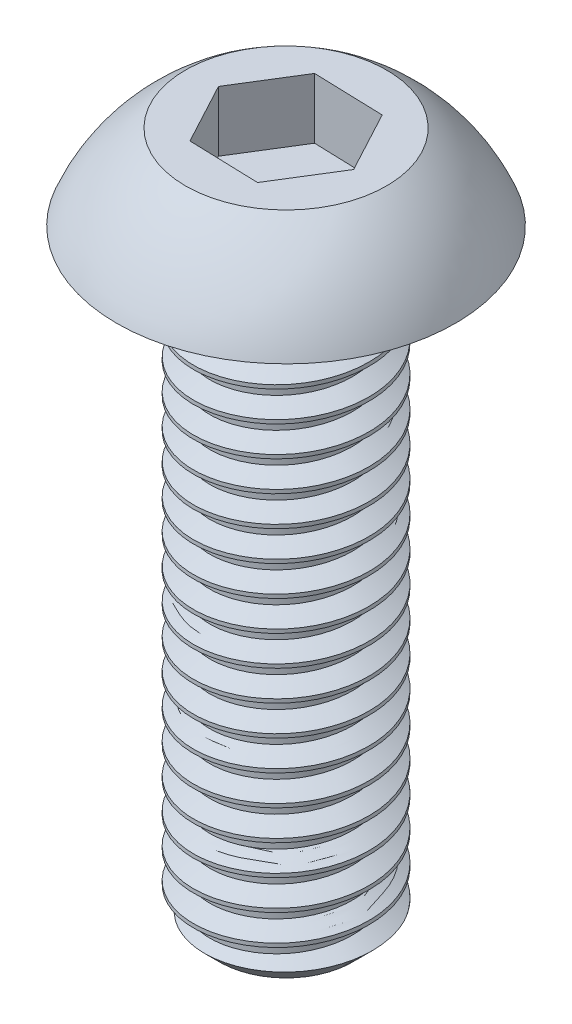
SolidWorks part; units mm, degrees
material "AISI 304"
ref_plane "Front Plane" through (0, 0, 0) normal (0, 0, 1) x (1, 0, 0)
ref_plane "Top Plane" through (0, 0, 0) normal (0, 1, 0) x (1, 0, 0)
ref_plane "Right Plane" through (0, 0, 0) normal (1, 0, 0) x (0, 0, -1)
sketch "Sketch1" plane through (0, 0, 0) normal (1, 0, 0) x (0, 0, -1)
  line L0 (0, 3.928) -> (0, 3.1683) construction
  line L1 (-2.8, 1.2683) -> (-1.45, 1.2683)
  line L2 (-1.45, 1.2683) -> (-1.45, -8.7317)
  line L3 (-1.6623, 2.6683) -> (0, 2.6683)
  line L4 (0, 2.6683) -> (0, -8.7317)
  line L5 (0, -8.7317) -> (-1.45, -8.7317)
  line L6 (0, 2.6683) -> (0, -3.4668) construction
  arc A0 (-2.8, 1.2683) -> (-1.6623, 2.6683) centre (0, 0.1552) cw
  point P10 (0, 3.1683)
  dimension "D1" = 2.9
  dimension "D2" = 5.6
  dimension "D3" = 1.9
  dimension "D4" = 10
  dimension "D5" = 1.4
revolve "Revolve1" add sketch "Sketch1" angle 360 about L0
sketch "Sketch2" plane through (0, 2.6683, 0) normal (0, 1, 0) x (1, 0, 0)
  line L1 (-0.5457, 1.0176) -> (-1.1541, 0.0363)
  line L2 (-1.1541, 0.0363) -> (-0.6085, -0.9814)
  line L3 (-0.6085, -0.9814) -> (0.5457, -1.0176)
  line L4 (0.5457, -1.0176) -> (1.1541, -0.0363)
  line L5 (1.1541, -0.0363) -> (0.6085, 0.9814)
  line L6 (0.6085, 0.9814) -> (-0.5457, 1.0176)
  circle A0 centre (0, 0) radius 1 construction
  dimension "D1" = 2
extrude "Cut-Extrude1" cut sketch "Sketch2" against normal blind 1
chamfer "Chamfer1" distance 0.35 angle 45 1 edges at (0, -8.7317, 1.45)
thread "Thread1" pitch 0.5 method cut profile "Thread Profile1" start angle 0, offset 0, length 20, pitch 0.5, diameter 2.9
ref_plane "Plane1" through (-1.45, 1.2683, 0) normal (0, 0, 1) x (-1, 0, 0)
sketch "Thread Profile1" plane through (-1.45, 1.2683, 0) normal (0, 0, 1) x (-1, 0, 0)
  line L0 (0, 0) -> (0, 0.5) construction
  line L11 (0, 0) -> (0, 0.4375)
  line L12 (0, 0.4375) -> (-0.2706, 0.2812)
  line L13 (-0.2706, 0.2812) -> (-0.2706, 0.1562)
  line L15 (-0.2706, 0.1562) -> (0, 0)
  line L17 (-0.2706, 0.2187) -> (0, 0.2187) construction
  point P2 (0, 0)
  dimension "Pitch" = 0.5
  dimension "Profile_Angle" = 60
  dimension "Profile_Land" = 0.125
  dimension "Profile_Height" = 0.2706
